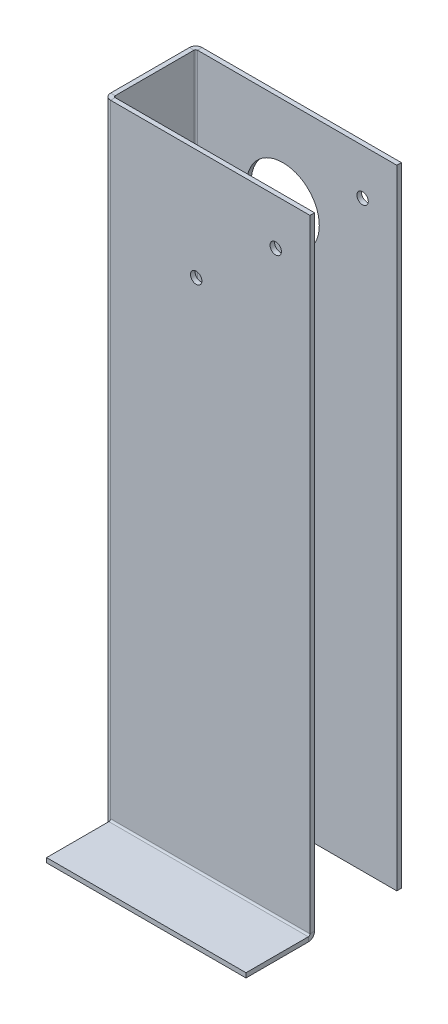
SolidWorks part; units mm, degrees
note: The reader was unsure of these and kept them because the rebuilt part matched: flange length of "Edge-Flange1", "Edge-Flange2", "Edge-Flange3".
ref_plane "Front Plane" through (0, 0, 0) normal (0, 0, 1) x (1, 0, 0)
ref_plane "Top Plane" through (0, 0, 0) normal (0, 1, 0) x (1, 0, 0)
ref_plane "Right Plane" through (0, 0, 0) normal (1, 0, 0) x (0, 0, -1)
sketch "Sketch1" plane through (0, 0, 0) normal (0, 0, 1) x (1, 0, 0)
  line L1 (0, 0) -> (90, 0)
  line L2 (0, 0) -> (0, 275)
  line L3 (0, 275) -> (90, 275)
  line L4 (90, 0) -> (90, 275)
  dimension "D1" = 90
  dimension "D2" = 275
base flange "Base-Flange1" sketch "Sketch1" thickness 2 reverse thickness direction no parameters "D1"=0.7366
edge flange "Edge-Flange1" sketch "Sketch8" flange angle 90 flange length 40 flange position material inside bend radius 0.7366 thickness 2 relief rectangular parameters "D6"=10
sketch "Sketch8" plane through (0, 0, -2) normal (-1, 0, 0) x (0, 1, 0)
  line L0 (275, 0) -> (0, 0) construction
  line L1 (275, 0) -> (0, 0)
  line L2 (0, 0) -> (0, 38)
  line L3 (0, 38) -> (275, 38)
  line L4 (275, 38) -> (275, 0)
bend "EdgeBend1" bend radius 0.7366 bend angle 90 parameters "D5"=1
edge flange "Edge-Flange2" sketch "Sketch11" flange angle 90 flange length 90 flange position material inside bend radius 0.7366 thickness 2 relief rectangular parameters "D6"=10
sketch "Sketch11" plane through (2, 0, -40) normal (0, 0, -1) x (0, 1, 0)
  line L0 (275, 0) -> (0, 0) construction
  line L1 (275, 0) -> (0, 0)
  line L2 (0, 0) -> (0, 88)
  line L3 (0, 88) -> (275, 88)
  line L4 (275, 88) -> (275, 0)
bend "EdgeBend2" bend radius 0.7366 bend angle 90 parameters "D5"=2
edge flange "Edge-Flange3" sketch "Sketch15" flange angle 90 flange length 30 flange position material inside bend radius 0.7366 thickness 2 relief none parameters "D6"=10
sketch "Sketch15" plane through (0, 0, 0) normal (0, -1, 0) x (1, 0, 0)
  line L0 (2.7366, 0) -> (90, 0) construction
  line L1 (2.7366, 0) -> (90, 0)
  line L2 (2.7366, 0) -> (2.7366, 28)
  line L3 (2.7366, 28) -> (90, 28)
  line L4 (90, 28) -> (90, 0)
bend "EdgeBend3" bend radius 0.7366 bend angle 90 parameters "D5"=3
sketch "Sketch18" plane through (0, 0, 0) normal (0, 0, 1) x (1, 0, 0)
  line L0 (90, 2.7366) -> (90, 275) construction
  line L1 (90, 275) -> (2.7366, 275) construction
  circle A0 centre (40.19, 226.48) radius 2.5
  circle A1 centre (75, 255) radius 2.5
  dimension "D2" = 48.52
  dimension "D3" = 5
  dimension "D4" = 15
  dimension "D5" = 20
  dimension "D1" = 49.81
extrude "Cut-Extrude2" cut sketch "Sketch18" against normal up to next normal cut yes
sketch "Sketch17" plane through (0, 0, -40) normal (0, 0, -1) x (-1, 0, 0)
  line L0 (-2.7366, 275) -> (-2.7366, 0) construction
  line L1 (-2.7366, 275) -> (-90, 275) construction
  circle A0 centre (-40.1866, 235.2) radius 15.875
  circle A1 centre (-75, 255) radius 2.5
  circle A2 centre (-75, 255) radius 2.5 construction
  dimension "D1" = 37.45
  dimension "D3" = 31.75
  dimension "D4" = 5
  dimension "D2" = 39.8
extrude "Cut-Extrude1" cut sketch "Sketch17" against normal up to next normal cut yes
sketch "Bend-Lines1" plane through (0, 0, 0) normal (0, 1, 0) x (1, 0, 0)
sketch "Bounding-Box1" plane through (0, 0, 0) normal (0, 1, 0) x (1, 0, 0)
sheet metal parameters "Sheet-Metal1" thickness 2 parameters "D1"=0.7366
flat pattern "Flat-Pattern1" [suppressed]
sketch "Bend-Lines2" plane through (0, 0, 0) normal (0, 1, 0) x (1, 0, 0)
sketch "Bounding-Box2" [suppressed] plane through (0, 0, 0) normal (0, 1, 0) x (1, 0, 0)
sheet metal parameters "Sheet-Metal2" thickness 2 parameters "D1"=0.7366
flat pattern "Flat-Pattern1" [suppressed]
sketch "Bend-Lines2" plane through (0, 0, 0) normal (0, 1, 0) x (1, 0, 0)
sketch "Bounding-Box2" [suppressed] plane through (0, 0, 0) normal (0, 1, 0) x (1, 0, 0)
bend of the flat pattern "Flatten-<EdgeBend1>1"
sheet metal parameters "Sheet-Metal3" thickness 2 parameters "D1"=0.7366
flat pattern "Flat-Pattern1" [suppressed]
sketch "Bend-Lines2" plane through (0, 0, 0) normal (0, 1, 0) x (1, 0, 0)
sketch "Bounding-Box2" [suppressed] plane through (0, 0, 0) normal (0, 1, 0) x (1, 0, 0)
bend of the flat pattern "Flatten-<EdgeBend1>1"
bend of the flat pattern "Flatten-<EdgeBend2>1"
sheet metal parameters "Sheet-Metal4" thickness 2 parameters "D1"=0.7366
flat pattern "Flat-Pattern1" [suppressed]
sketch "Bend-Lines2" plane through (0, 0, 0) normal (0, 1, 0) x (1, 0, 0)
sketch "Bounding-Box2" [suppressed] plane through (0, 0, 0) normal (0, 1, 0) x (1, 0, 0)
bend of the flat pattern "Flatten-<EdgeBend1>1"
bend of the flat pattern "Flatten-<EdgeBend2>1"
bend of the flat pattern "Flatten-<EdgeBend3>1"
sheet metal parameters "Sheet-Metal5" thickness 2 parameters "D1"=0.7366
flat pattern "Flat-Pattern1" [suppressed]
sketch "Bend-Lines2" plane through (0, 0, 0) normal (0, 1, 0) x (1, 0, 0)
sketch "Bounding-Box2" [suppressed] plane through (0, 0, 0) normal (0, 1, 0) x (1, 0, 0)
bend of the flat pattern "Flatten-<EdgeBend1>1"
bend of the flat pattern "Flatten-<EdgeBend2>1"
bend of the flat pattern "Flatten-<EdgeBend3>1"
sheet metal parameters "Sheet-Metal6" thickness 2 parameters "D1"=0.7366
flat pattern "Flat-Pattern1" [suppressed]
sketch "Bend-Lines2" plane through (0, 0, 0) normal (0, 1, 0) x (1, 0, 0)
sketch "Bounding-Box2" [suppressed] plane through (0, 0, 0) normal (0, 1, 0) x (1, 0, 0)
bend of the flat pattern "Flatten-<EdgeBend1>1"
bend of the flat pattern "Flatten-<EdgeBend2>1"
bend of the flat pattern "Flatten-<EdgeBend3>1"
